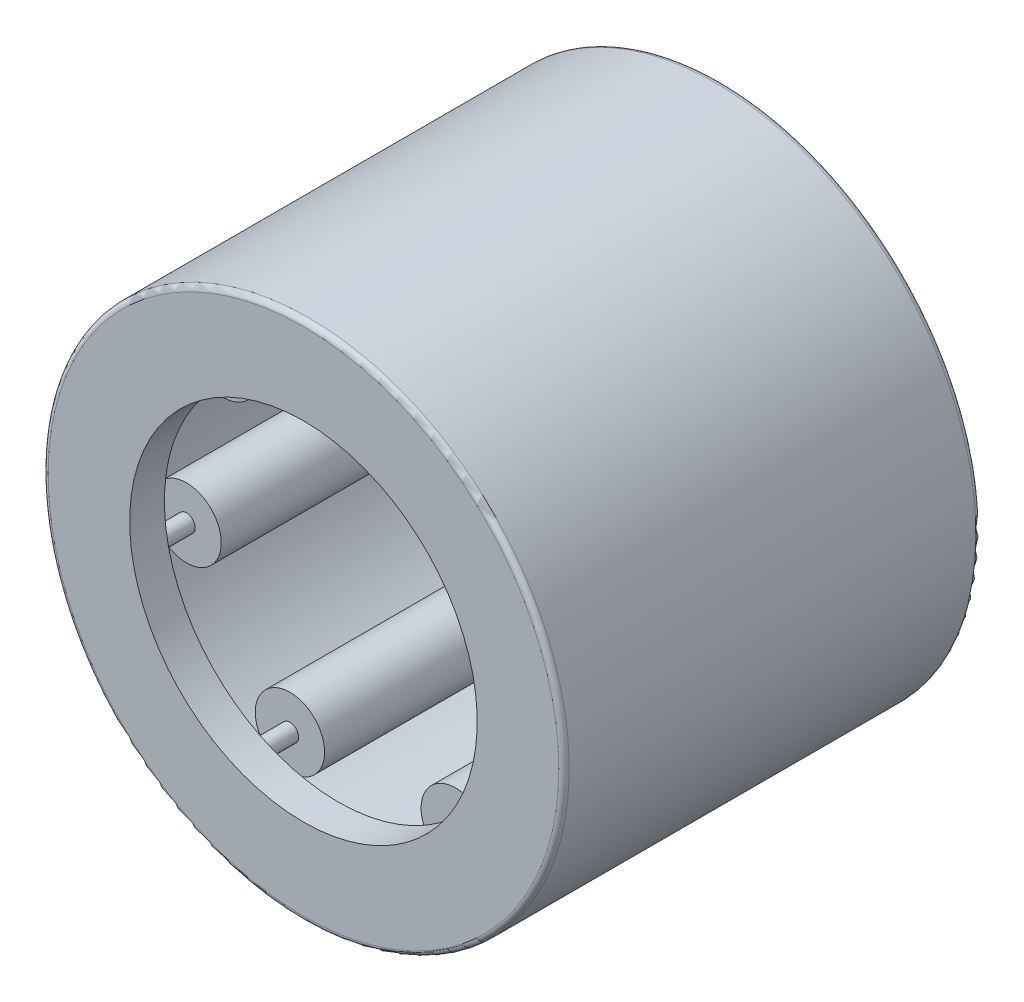
SolidWorks part; units mm, degrees
ref_plane "Front Plane" through (0, 0, 0) normal (0, 0, 1) x (1, 0, 0)
ref_plane "Top Plane" through (0, 0, 0) normal (0, 1, 0) x (1, 0, 0)
ref_plane "Right Plane" through (0, 0, 0) normal (1, 0, 0) x (0, 0, -1)
sketch "Sketch1" plane through (0, 0, 0) normal (1, 0, 0) x (0, 0, -1)
  line L0 (-4, 0) -> (4, 0) construction
  line L1 (0, 0) -> (0, 4.9965) construction
  line L2 (-4, 0) -> (-4, 4.9965) construction
  line L3 (-4, 4.9965) -> (4, 4.9965)
  line L4 (4, 4.9965) -> (4, 0) construction
  line L5 (4, 0) -> (3.3345, 0) construction
  line L6 (3.3345, 0) -> (3.3345, 4.331) construction
  line L7 (3.3345, 4.331) -> (-3.3345, 4.331)
  line L8 (-3.3345, 4.331) -> (-3.3345, 0) construction
  line L9 (-3.3345, 0) -> (-4, 0) construction
  line L10 (-4, 4.9965) -> (-4, 3.3327)
  line L11 (-4, 3.3327) -> (-3.3345, 3.3327)
  line L12 (-3.3345, 3.3327) -> (-3.3345, 4.331)
  line L13 (3.3345, 4.9965) -> (3.3345, 4.331) construction
  line L14 (3.3345, 4.331) -> (3.3345, 3.3327)
  line L15 (3.3345, 3.3327) -> (4, 3.3327)
  line L16 (4, 3.3327) -> (4, 4.9965)
  line L17 (3.3345, 4.331) -> (3.3345, 3.6655) construction
  line L18 (3.3345, 3.6655) -> (3.3345, 3) construction
  line L19 (3.3345, -4.331) -> (3.3345, -3.6655) construction
  line L20 (3.3345, -4.9965) -> (3.3345, -4.331) construction
  line L21 (4, -3.3327) -> (4, -4.9965) construction
  line L22 (3.3345, -3.3327) -> (4, -3.3327) construction
  line L23 (3.3345, -4.331) -> (3.3345, -3.3327) construction
  line L24 (-3.3345, -3.3327) -> (-3.3345, -4.331) construction
  line L25 (-4, -3.3327) -> (-3.3345, -3.3327) construction
  line L26 (-4, -4.9965) -> (-4, -3.3327) construction
  line L27 (3.3345, -4.331) -> (-3.3345, -4.331) construction
  line L28 (-4, -4.9965) -> (4, -4.9965) construction
  point P5 (0, 3)
  dimension "Width" = 8
  dimension "OD" = 9.993
  dimension "Shaft Dia" = 6
revolve "Revolve1" add sketch "Sketch1" angle 360 about L0
sketch "Sketch2" plane through (0, 0, 0) normal (1, 0, 0) x (0, 0, -1)
  line L0 (3.3345, 4.331) -> (-3.3345, 4.331) construction
  line L1 (-2.669, 3.6655) -> (2.669, 3.6655) construction
  line L2 (-2.669, 3.6655) -> (-2.669, 4.331) construction
  line L3 (-2.669, 4.331) -> (2.669, 4.331)
  line L4 (2.669, 3.6655) -> (2.669, 4.331) construction
  line L5 (3.3345, 3.3327) -> (4, 3.3327) construction
  line L6 (-3.3345, 3.6655) -> (-2.669, 3.6655) construction
  line L7 (2.669, 3.6655) -> (3.3345, 3.6655) construction
  line L8 (-4, 3.3327) -> (-3.3345, 3.3327) construction
  line L9 (-2.669, 3.8319) -> (-2.669, 3.4991) construction
  line L10 (-3.3345, 3.6655) -> (-3.3345, 3.3327) construction
  line L11 (-2.669, 4.331) -> (-2.669, 3.8319)
  line L12 (2.669, 4.331) -> (2.669, 3.8319)
  line L13 (2.669, 3.8319) -> (-2.669, 3.8319)
  line L14 (0, 4.331) -> (0, 3) construction
  line L15 (-3.3345, 3.3327) -> (-3.3345, 4.331) construction
  line L16 (-2.669, 3.4991) -> (-3.3345, 3.4991) construction
  line L17 (0, 0) -> (4, 0) construction
  line L18 (-2.669, -3.4991) -> (-3.3345, -3.4991) construction
  line L19 (0, -4.331) -> (0, -3) construction
  line L20 (-3.3345, -3.6655) -> (-3.3345, -3.3327) construction
  line L21 (-2.669, -3.8319) -> (-2.669, -3.4991) construction
  line L22 (2.669, -3.6655) -> (3.3345, -3.6655) construction
  line L23 (-3.3345, -3.6655) -> (-2.669, -3.6655) construction
  line L24 (2.669, -3.6655) -> (2.669, -4.331) construction
  line L25 (-2.669, -3.6655) -> (-2.669, -4.331) construction
  line L26 (-2.669, -3.6655) -> (2.669, -3.6655) construction
  line L27 (2.669, -3.8319) -> (-2.669, -3.8319) construction
  line L28 (2.669, -4.331) -> (2.669, -3.8319) construction
  line L29 (-2.669, -4.331) -> (-2.669, -3.8319) construction
  line L30 (-2.669, -4.331) -> (2.669, -4.331) construction
  line L31 (4, -4.9965) -> (4, 4.9965) construction
  line L32 (3.3345, 4.331) -> (3.3345, 3.3327) construction
  point P16 (0, 3.6655)
revolve "Revolve2" add sketch "Sketch2" angle 360 about L1
sketch "Sketch3" plane through (0, 0, 0) normal (1, 0, 0) x (0, 0, -1)
  line L0 (3.3345, 4.331) -> (3.3345, 3.3327) construction
  line L1 (-3.3345, 3.6655) -> (3.3345, 3.6655)
  line L2 (-3.3345, 3.6655) -> (-3.3345, 3.8319)
  line L3 (-3.3345, 3.8319) -> (3.3345, 3.8319)
  line L4 (3.3345, 3.6655) -> (3.3345, 3.8319)
  line L5 (0, 0) -> (4, 0) construction
  line L6 (4, -4.9965) -> (4, 4.9965) construction
  line L7 (3.3345, -3.6655) -> (3.3345, -3.8319) construction
  line L8 (-3.3345, -3.8319) -> (3.3345, -3.8319) construction
  line L9 (-3.3345, -3.6655) -> (-3.3345, -3.8319) construction
  line L10 (-3.3345, -3.6655) -> (3.3345, -3.6655) construction
revolve "Revolve3" add sketch "Sketch3" angle 360 about L1
ref_axis "Axis1" through (0, 0, -4) along (0, 0, 1)
pattern_circular "CirPattern1" count 7 every 51.429 about axis through (0, 0, -4) along (0, 0, 1) of bodies 167 166
fillet "Fillet1" radius 0.0999 2 edges at (0, -4.9965, -4) (0, -4.9965, 4)
sketch "Sketch4" plane through (0, 0, 0) normal (1, 0, 0) x (0, 0, -1)
  line L0 (2.669, 4.331) -> (2.669, 3.8319) construction
  line L1 (3.9001, 3) -> (2.669, 3)
  line L2 (3.9001, 3) -> (3.9001, 3.3327)
  line L3 (3.9001, 3.3327) -> (2.669, 3.3327)
  line L4 (2.669, 3) -> (2.669, 3.3327)
  line L5 (-4, 3.3327) -> (-3.3345, 3.3327) construction
  line L6 (3.9001, -4.9965) -> (3.9001, 4.9965) construction
revolve "Revolve4" [suppressed] add sketch "Sketch4" angle 360 about L0
sketch "Sketch5" plane through (0, 0, 0) normal (1, 0, 0) x (0, 0, -1)
  line L0 (-3.9001, 4.9965) -> (-3.9001, -4.9965) construction
  line L1 (-2.669, 3) -> (-3.9001, 3)
  line L2 (-2.669, 3) -> (-2.669, 3.3327)
  line L3 (-2.669, 3.3327) -> (-3.9001, 3.3327)
  line L4 (-3.9001, 3) -> (-3.9001, 3.3327)
  line L5 (-2.669, 4.331) -> (-2.669, 3.8319) construction
revolve "Revolve5" [suppressed] add sketch "Sketch5" angle 360 about L0
sketch "Sketch6" plane through (0, 0, 0) normal (0, 0, 1) x (1, 0, 0)
  circle A0 centre (0, 0) radius 3 construction
equation "\"Rollers@CirPattern1\" = \"OD@Sketch1\"*.75"
equation "\"D1@Fillet1\" = \"OD@Sketch1\"*.01"
equation "\"Angle@CirPattern1\"= 360 / \"Rollers@CirPattern1\""
